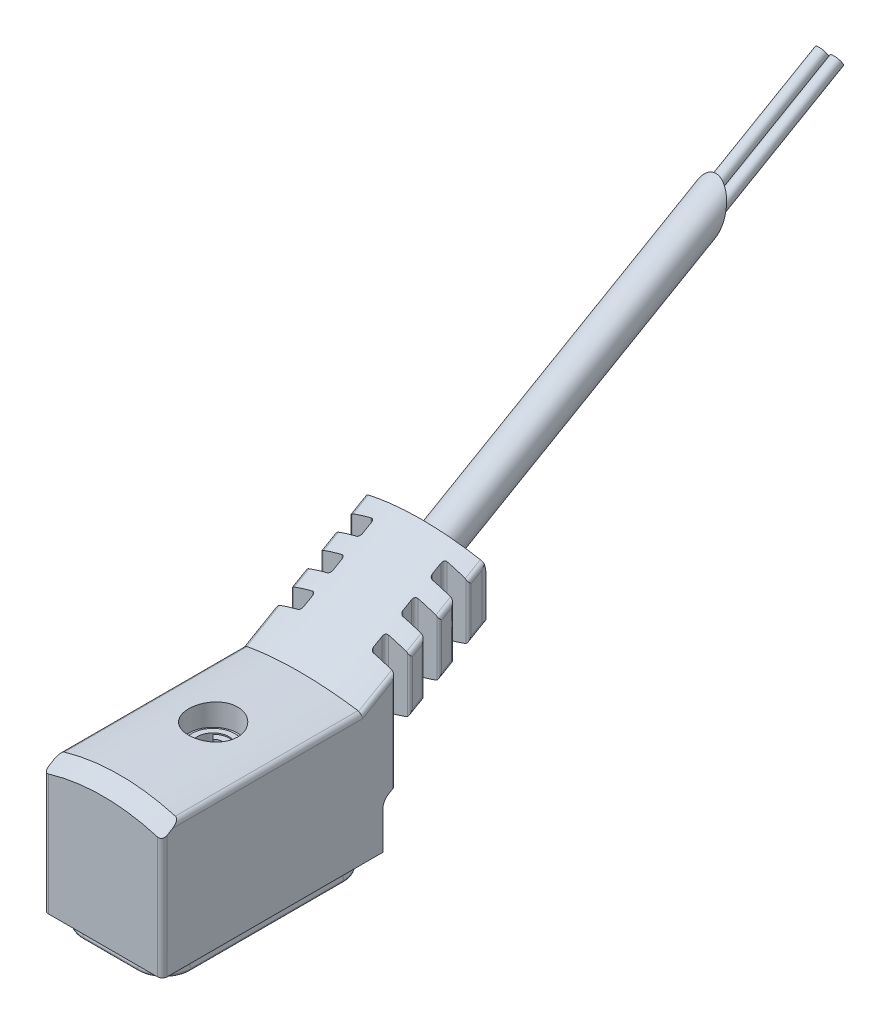
SolidWorks part; units mm, degrees
ref_plane "Front Plane" through (0, 0, 0) normal (0, 0, 1) x (1, 0, 0)
ref_plane "Top Plane" through (0, 0, 0) normal (0, 1, 0) x (1, 0, 0)
ref_plane "Right Plane" through (0, 0, 0) normal (1, 0, 0) x (0, 0, -1)
ref_plane "Plane1" through (0, 0, 0.2) normal (0, 0, 1) x (1, 0, 0)
ref_plane "Plane2" through (0, -0.0866, 0.15) normal (0, -0.5, 0.866) x (1, 0, 0)
sketch "Sketch1" plane through (0, 0, 0) normal (1, 0, 0) x (0, 0, -1)
  line L0 (-9.4, 11.35) -> (-9.4, 0)
  line L1 (-9.4, 0) -> (8.6, 0)
  line L2 (8.6, 0) -> (8.6, 3.0453)
  line L3 (9.1, 3.9113) -> (9.6, 4.2)
  line L4 (9.6, 4.2) -> (9.6, 11.35)
  line L5 (9.6, 11.35) -> (-9.4, 11.35)
  arc A0 (8.6, 3.0453) -> (9.1, 3.9113) centre (9.6, 3.0453) cw
extrude "Boss-Extrude1" add sketch "Sketch1" against normal blind 4.85 and the other way blind 4.85
sketch "Sketch2" plane through (0, 0, 0.2) normal (0, 0, 1) x (1, 0, 0)
  line L0 (-6, 15) -> (-6, 0)
  line L1 (-6, 0) -> (-4.85, 0)
  line L2 (-4.85, 0) -> (-4.85, 10.2729)
  line L3 (4.85, 10.2729) -> (4.85, 0)
  line L4 (4.85, 0) -> (6, 0)
  line L5 (6, 0) -> (6, 15)
  line L6 (6, 15) -> (-6, 15)
  arc A0 (-4.85, 10.2729) -> (-4.5257, 10.705) centre (-4.4, 10.2729) cw
  arc A1 (-4.5257, 10.705) -> (4.5257, 10.705) centre (0, -4.85) cw
  arc A2 (4.5257, 10.705) -> (4.85, 10.2729) centre (4.4, 10.2729) cw
extrude "Cut-Extrude1" cut sketch "Sketch2" along normal blind 10 and the other way blind 10
sketch "Sketch3" plane through (0, 0, 0) normal (0, 1, 0) x (1, 0, 0)
  line L0 (-8, 12.8) -> (-8, -12.2)
  line L1 (-8, -12.2) -> (8, -12.2)
  line L2 (8, -12.2) -> (8, 12.8)
  line L3 (8, 12.8) -> (-8, 12.8)
  line L4 (-4.45, -9.4) -> (4.45, -9.4)
  line L5 (4.85, -9) -> (4.85, 9.4)
  line L6 (4.65, 9.6) -> (-4.65, 9.6)
  line L7 (-4.85, 9.4) -> (-4.85, -9)
  arc A0 (-4.85, -9) -> (-4.45, -9.4) centre (-4.45, -9) ccw
  arc A1 (4.45, -9.4) -> (4.85, -9) centre (4.45, -9) ccw
  arc A2 (4.85, 9.4) -> (4.65, 9.6) centre (4.65, 9.4) ccw
  arc A3 (-4.65, 9.6) -> (-4.85, 9.4) centre (-4.65, 9.4) ccw
extrude "Cut-Extrude2" cut sketch "Sketch3" along normal blind 10
sketch "Sketch4" plane through (0, -0.0866, 0.15) normal (0, -0.5, 0.866) x (1, 0, 0)
  line L0 (4.85, 2.2157) -> (4.85, 5.4263)
  line L1 (-4.85, 5.4263) -> (-4.85, 2.2157)
  arc A0 (-4.85, 2.2157) -> (-4.5719, 1.8347) centre (-4.45, 2.2157) ccw
  arc A1 (-4.5719, 1.8347) -> (4.5719, 1.8347) centre (0, 16.121) ccw
  arc A2 (4.5719, 1.8347) -> (4.85, 2.2157) centre (4.45, 2.2157) ccw
  arc A3 (4.85, 5.4263) -> (4.5719, 5.8073) centre (4.45, 5.4263) ccw
  arc A4 (4.5719, 5.8073) -> (-4.5719, 5.8073) centre (0, -8.479) ccw
  arc A5 (-4.5719, 5.8073) -> (-4.85, 5.4263) centre (-4.45, 5.4263) ccw
extrude "Boss-Extrude2" add sketch "Sketch4" against normal blind 25
sketch "Sketch5" plane through (0, 0, 0) normal (1, 0, 0) x (0, 0, -1)
  line L0 (-9.4, 12.35) -> (-9.4, 10.55)
  line L1 (-9.4, 10.55) -> (-6.2823, 12.35)
  line L2 (-6.2823, 12.35) -> (-9.4, 12.35)
  line L3 (1.8, -4.85) -> (-2.2, -4.85) construction
revolve "Cut-Revolve1" cut sketch "Sketch5" angle 19 about L3 other way angle 19 reverse direction yes
sketch "Sketch6" plane through (0, 0, 0) normal (1, 0, 0) x (0, 0, -1)
  line L0 (15.8637, 19.2407) -> (17.5, 14.516)
  line L1 (17.5, 14.516) -> (17.5, 5)
  line L2 (17.5, 5) -> (32.5, 5)
  line L3 (32.5, 5) -> (32.5, 20)
  line L4 (32.5, 20) -> (17.5, 20)
  line L5 (17.5, 20) -> (15.8637, 19.2407)
extrude "Cut-Extrude3" cut sketch "Sketch6" along normal blind 5 and the other way blind 5
sketch "Sketch7" plane through (0, 0, 0) normal (0, 1, 0) x (1, 0, 0)
  line L0 (-6, 7.8) -> (-4.85, 7.8)
  line L1 (-4.85, 7.8) -> (-4.85, 9.4)
  line L2 (-4.65, 9.6) -> (-3.1, 9.6)
  line L3 (-2.85, 9.85) -> (-2.85, 10.55)
  line L4 (-3.1, 10.8) -> (-4.65, 10.8)
  line L5 (-4.85, 11) -> (-4.85, 11.8)
  line L6 (-4.65, 12) -> (-3.1, 12)
  line L7 (-2.85, 12.25) -> (-2.85, 12.95)
  line L8 (-3.1, 13.2) -> (-4.65, 13.2)
  line L9 (-4.85, 13.4) -> (-4.85, 14.2)
  line L10 (-4.65, 14.4) -> (-3.1, 14.4)
  line L11 (-2.85, 14.65) -> (-2.85, 15.35)
  line L12 (-3.1, 15.6) -> (-4.65, 15.6)
  line L13 (-4.85, 15.8) -> (-4.85, 16.7)
  line L14 (-4.05, 17.5) -> (4.05, 17.5)
  line L15 (4.85, 16.7) -> (4.85, 15.8)
  line L16 (4.65, 15.6) -> (3.1, 15.6)
  line L17 (2.85, 15.35) -> (2.85, 14.65)
  line L18 (3.1, 14.4) -> (4.65, 14.4)
  line L19 (4.85, 14.2) -> (4.85, 13.4)
  line L20 (4.65, 13.2) -> (3.1, 13.2)
  line L21 (2.85, 12.95) -> (2.85, 12.25)
  line L22 (3.1, 12) -> (4.65, 12)
  line L23 (4.85, 11.8) -> (4.85, 11)
  line L24 (4.65, 10.8) -> (3.1, 10.8)
  line L25 (2.85, 10.55) -> (2.85, 9.85)
  line L26 (3.1, 9.6) -> (4.65, 9.6)
  line L27 (4.85, 9.4) -> (4.85, 7.8)
  line L28 (4.85, 7.8) -> (6, 7.8)
  line L29 (6, 7.8) -> (6, 19.8)
  line L30 (6, 19.8) -> (-6, 19.8)
  line L31 (-6, 19.8) -> (-6, 7.8)
  arc A0 (-4.85, 9.4) -> (-4.65, 9.6) centre (-4.65, 9.4) cw
  arc A1 (-3.1, 9.6) -> (-2.85, 9.85) centre (-3.1, 9.85) ccw
  arc A2 (-2.85, 10.55) -> (-3.1, 10.8) centre (-3.1, 10.55) ccw
  arc A3 (-4.65, 10.8) -> (-4.85, 11) centre (-4.65, 11) cw
  arc A4 (-4.85, 11.8) -> (-4.65, 12) centre (-4.65, 11.8) cw
  arc A5 (-3.1, 12) -> (-2.85, 12.25) centre (-3.1, 12.25) ccw
  arc A6 (-2.85, 12.95) -> (-3.1, 13.2) centre (-3.1, 12.95) ccw
  arc A7 (-4.65, 13.2) -> (-4.85, 13.4) centre (-4.65, 13.4) cw
  arc A8 (-4.85, 14.2) -> (-4.65, 14.4) centre (-4.65, 14.2) cw
  arc A9 (-3.1, 14.4) -> (-2.85, 14.65) centre (-3.1, 14.65) ccw
  arc A10 (-2.85, 15.35) -> (-3.1, 15.6) centre (-3.1, 15.35) ccw
  arc A11 (-4.65, 15.6) -> (-4.85, 15.8) centre (-4.65, 15.8) cw
  arc A12 (-4.85, 16.7) -> (-4.05, 17.5) centre (-4.05, 16.7) cw
  arc A13 (4.05, 17.5) -> (4.85, 16.7) centre (4.05, 16.7) cw
  arc A14 (4.85, 15.8) -> (4.65, 15.6) centre (4.65, 15.8) cw
  arc A15 (3.1, 15.6) -> (2.85, 15.35) centre (3.1, 15.35) ccw
  arc A16 (2.85, 14.65) -> (3.1, 14.4) centre (3.1, 14.65) ccw
  arc A17 (4.65, 14.4) -> (4.85, 14.2) centre (4.65, 14.2) cw
  arc A18 (4.85, 13.4) -> (4.65, 13.2) centre (4.65, 13.4) cw
  arc A19 (3.1, 13.2) -> (2.85, 12.95) centre (3.1, 12.95) ccw
  arc A20 (2.85, 12.25) -> (3.1, 12) centre (3.1, 12.25) ccw
  arc A21 (4.65, 12) -> (4.85, 11.8) centre (4.65, 11.8) cw
  arc A22 (4.85, 11) -> (4.65, 10.8) centre (4.65, 11) cw
  arc A23 (3.1, 10.8) -> (2.85, 10.55) centre (3.1, 10.55) ccw
  arc A24 (2.85, 9.85) -> (3.1, 9.6) centre (3.1, 9.85) ccw
  arc A25 (4.65, 9.6) -> (4.85, 9.4) centre (4.65, 9.4) cw
extrude "Cut-Extrude4" cut sketch "Sketch7" along normal blind 18
sketch "Sketch8" plane through (0, 0, 0) normal (1, 0, 0) x (0, 0, -1)
  line L0 (-8.8263, -1) -> (8.0263, -1)
  line L1 (8.0263, -1) -> (7.85, 0)
  line L2 (7.85, 0) -> (-8.65, 0)
  line L3 (-8.65, 0) -> (-8.8263, -1)
extrude "Boss-Extrude3" add sketch "Sketch8" against normal blind 4.45 and the other way blind 4.45
sketch "Sketch9" plane through (0, 0, 0.2) normal (0, 0, 1) x (1, 0, 0)
  line L0 (-6, -3) -> (6, -3)
  line L1 (6, -3) -> (6, 0)
  line L2 (6, 0) -> (4.25, 0)
  line L3 (4.25, 0) -> (4.4263, -1)
  line L4 (4.4263, -1) -> (-4.4263, -1)
  line L5 (-4.4263, -1) -> (-4.25, 0)
  line L6 (-4.25, 0) -> (-6, 0)
  line L7 (-6, 0) -> (-6, -3)
extrude "Cut-Extrude5" cut sketch "Sketch9" along normal blind 9 and the other way blind 9
sketch "Sketch10" plane through (0, -0.0866, 0.15) normal (0, -0.5, 0.866) x (1, 0, 0)
  circle A0 centre (0, 3.821) radius 1.45
extrude "Boss-Extrude4" add sketch "Sketch10" against normal blind 50.5
sketch "Sketch11" plane through (0, 0, 0) normal (1, 0, 0) x (0, 0, -1)
  line L0 (37.3798, 20.6031) -> (42.0783, 18.893)
  line L1 (42.0783, 18.893) -> (45.4985, 28.2899)
  line L2 (45.4985, 28.2899) -> (40.8, 30)
  line L3 (40.8, 30) -> (37.3798, 20.6031)
extrude "Cut-Extrude6" cut sketch "Sketch11" along normal blind 3 and the other way blind 3
ref_plane "Plane3" through (0, 0, 6.65) normal (0, 0, 1) x (1, 0, 0)
sketch "Sketch12" plane through (0, 0, 6.65) normal (0, 0, 1) x (1, 0, 0)
  line L0 (-2.25, -3) -> (-6, -3)
  line L1 (-6, -3) -> (-6, 0)
  line L2 (-6, 0) -> (-4.25, 0)
  line L3 (-4.25, 0) -> (-4.3953, -0.824)
  line L4 (-4.2476, -1) -> (-2.25, -1)
  line L5 (-2.25, -1) -> (-2.25, -3)
  line L6 (-2.25, -1) -> (-2.25, -3) construction
  arc A0 (-4.3953, -0.824) -> (-4.2476, -1) centre (-4.2476, -0.85) ccw
revolve "Cut-Revolve2" cut sketch "Sketch12" angle 90 about L6 reverse direction yes
ref_plane "Plane4" through (0, 0, -5.85) normal (0, 0, 1) x (1, 0, 0)
sketch "Sketch13" plane through (0, 0, -5.85) normal (0, 0, 1) x (1, 0, 0)
  line L0 (-6, -3) -> (6, -3)
  line L1 (6, -3) -> (6, 0)
  line L2 (6, 0) -> (4.25, 0)
  line L3 (4.25, 0) -> (4.3953, -0.824)
  line L4 (4.2476, -1) -> (-4.2476, -1)
  line L5 (-4.3953, -0.824) -> (-4.25, 0)
  line L6 (-4.25, 0) -> (-6, 0)
  line L7 (-6, 0) -> (-6, -3)
  arc A0 (4.3953, -0.824) -> (4.2476, -1) centre (4.2476, -0.85) cw
  arc A1 (-4.2476, -1) -> (-4.3953, -0.824) centre (-4.2476, -0.85) cw
extrude "Cut-Extrude7" cut sketch "Sketch13" along normal blind 12.5
sketch "Sketch14" plane through (0, 0, 0) normal (1, 0, 0) x (0, 0, -1)
  line L0 (-10.2, -2) -> (9.8, -2)
  line L1 (9.8, -2) -> (9.8, 0)
  line L2 (9.8, 0) -> (7.85, 0)
  line L3 (7.85, 0) -> (7.9953, -0.824)
  line L4 (7.8476, -1) -> (-8.6476, -1)
  line L5 (-8.7953, -0.824) -> (-8.65, 0)
  line L6 (-8.65, 0) -> (-10.2, 0)
  line L7 (-10.2, 0) -> (-10.2, -2)
  arc A0 (7.9953, -0.824) -> (7.8476, -1) centre (7.8476, -0.85) cw
  arc A1 (-8.6476, -1) -> (-8.7953, -0.824) centre (-8.6476, -0.85) cw
extrude "Cut-Extrude8" cut sketch "Sketch14" along normal blind 6.45 and the other way blind 6.45
sketch "Sketch15" plane through (0, 0, 6.65) normal (0, 0, 1) x (1, 0, 0)
  line L0 (2.25, -1) -> (4.2476, -1)
  line L1 (4.3953, -0.824) -> (4.25, 0)
  line L2 (4.25, 0) -> (6, 0)
  line L3 (6, 0) -> (6, -3)
  line L4 (6, -3) -> (2.25, -3)
  line L5 (2.25, -3) -> (2.25, -1)
  line L6 (2.25, -3) -> (2.25, -1) construction
  arc A0 (4.2476, -1) -> (4.3953, -0.824) centre (4.2476, -0.85) ccw
revolve "Cut-Revolve3" cut sketch "Sketch15" angle 90 about L6 reverse direction yes
ref_plane "Plane5" through (0, 0, -5.85) normal (0, 0, 1) x (1, 0, 0)
sketch "Sketch16" plane through (0, 0, -5.85) normal (0, 0, 1) x (1, 0, 0)
  line L0 (2.25, -1) -> (4.2476, -1)
  line L1 (4.3953, -0.824) -> (4.25, 0)
  line L2 (4.25, 0) -> (6, 0)
  line L3 (6, 0) -> (6, -3)
  line L4 (6, -3) -> (2.25, -3)
  line L5 (2.25, -3) -> (2.25, -1)
  line L6 (2.25, -3) -> (2.25, -1) construction
  arc A0 (4.2476, -1) -> (4.3953, -0.824) centre (4.2476, -0.85) ccw
revolve "Cut-Revolve4" cut sketch "Sketch16" angle 90 about L6
sketch "Sketch17" plane through (0, 0, -5.85) normal (0, 0, 1) x (1, 0, 0)
  line L0 (-2.25, -3) -> (-6, -3)
  line L1 (-6, -3) -> (-6, 0)
  line L2 (-6, 0) -> (-4.25, 0)
  line L3 (-4.25, 0) -> (-4.3953, -0.824)
  line L4 (-4.2476, -1) -> (-2.25, -1)
  line L5 (-2.25, -1) -> (-2.25, -3)
  line L6 (-2.25, -1) -> (-2.25, -3) construction
  arc A0 (-4.3953, -0.824) -> (-4.2476, -1) centre (-4.2476, -0.85) ccw
revolve "Cut-Revolve5" cut sketch "Sketch17" angle 90 about L6
sketch "Sketch18" plane through (0, 0, 0) normal (1, 0, 0) x (0, 0, -1)
  line L0 (-8.6168, -1) -> (7.8168, -1)
  line L1 (7.7276, -0.9451) -> (7.25, 0)
  line L2 (7.25, 0) -> (-8.05, 0)
  line L3 (-8.05, 0) -> (-8.5276, -0.9451)
  arc A0 (7.8168, -1) -> (7.7276, -0.9451) centre (7.8168, -0.9) cw
  arc A1 (-8.5276, -0.9451) -> (-8.6168, -1) centre (-8.6168, -0.9) cw
extrude "Cut-Extrude9" cut sketch "Sketch18" along normal blind 2.25 and the other way blind 2.25
ref_plane "Plane6" through (0, 0, -5.85) normal (0, 0, 1) x (1, 0, 0)
sketch "Sketch19" plane through (0, 0, -5.85) normal (0, 0, 1) x (1, 0, 0)
  line L0 (-4.2168, -1) -> (4.2168, -1)
  line L1 (4.1276, -0.9451) -> (3.65, 0)
  line L2 (3.65, 0) -> (-3.65, 0)
  line L3 (-3.65, 0) -> (-4.1276, -0.9451)
  arc A0 (4.2168, -1) -> (4.1276, -0.9451) centre (4.2168, -0.9) cw
  arc A1 (-4.1276, -0.9451) -> (-4.2168, -1) centre (-4.2168, -0.9) cw
extrude "Cut-Extrude10" cut sketch "Sketch19" along normal blind 12.5
sketch "Sketch20" plane through (0, 0, 6.65) normal (0, 0, 1) x (1, 0, 0)
  line L0 (-2.25, -1) -> (-4.2168, -1)
  line L1 (-4.1276, -0.9451) -> (-3.65, 0)
  line L2 (-3.65, 0) -> (-2.25, 0)
  line L3 (-2.25, 0) -> (-2.25, -1)
  line L4 (-2.25, 0) -> (-2.25, -1) construction
  arc A0 (-4.2168, -1) -> (-4.1276, -0.9451) centre (-4.2168, -0.9) ccw
revolve "Cut-Revolve6" cut sketch "Sketch20" angle 360 about L4
sketch "Sketch21" plane through (0, 0, 6.65) normal (0, 0, 1) x (1, 0, 0)
  line L0 (2.25, 0) -> (3.65, 0)
  line L1 (3.65, 0) -> (4.1276, -0.9451)
  line L2 (4.2168, -1) -> (2.25, -1)
  line L3 (2.25, -1) -> (2.25, 0)
  line L4 (2.25, -1) -> (2.25, 0) construction
  arc A0 (4.1276, -0.9451) -> (4.2168, -1) centre (4.2168, -0.9) ccw
revolve "Cut-Revolve7" cut sketch "Sketch21" angle 360 about L4
sketch "Sketch22" plane through (0, 0, -5.85) normal (0, 0, 1) x (1, 0, 0)
  line L0 (-2.25, -1) -> (-4.2168, -1)
  line L1 (-4.1276, -0.9451) -> (-3.65, 0)
  line L2 (-3.65, 0) -> (-2.25, 0)
  line L3 (-2.25, 0) -> (-2.25, -1)
  line L4 (-2.25, 0) -> (-2.25, -1) construction
  arc A0 (-4.2168, -1) -> (-4.1276, -0.9451) centre (-4.2168, -0.9) ccw
revolve "Cut-Revolve8" cut sketch "Sketch22" angle 360 about L4
sketch "Sketch23" plane through (0, 0, -5.85) normal (0, 0, 1) x (1, 0, 0)
  line L0 (2.25, 0) -> (3.65, 0)
  line L1 (3.65, 0) -> (4.1276, -0.9451)
  line L2 (4.2168, -1) -> (2.25, -1)
  line L3 (2.25, -1) -> (2.25, 0)
  line L4 (2.25, -1) -> (2.25, 0) construction
  arc A0 (4.1276, -0.9451) -> (4.2168, -1) centre (4.2168, -0.9) ccw
revolve "Cut-Revolve9" cut sketch "Sketch23" angle 360 about L4
sketch "Sketch24" plane through (0, 0, 0) normal (1, 0, 0) x (0, 0, -1)
  line L0 (-0.4, 0) -> (-2.5, 0)
  line L1 (-2.5, 0) -> (-2.4651, 2)
  line L2 (-2.4651, 2) -> (-1.5425, 2)
  line L3 (-1.5425, 2) -> (-1.45, 7.3)
  line L4 (-1.45, 7.3) -> (-1.45, 8.5)
  line L5 (-1.45, 8.5) -> (-1.7, 8.5)
  line L6 (-1.7, 8.5) -> (-1.7, 9.6)
  line L7 (-1.7, 9.6) -> (-2.15, 9.6)
  line L8 (-2.15, 9.6) -> (-2.2, 9.55)
  line L9 (-2.2, 9.55) -> (-2.2, 9.5)
  line L10 (-2.2, 9.5) -> (-2.4, 9.5)
  line L11 (-2.4, 9.5) -> (-2.4, 11.35)
  line L12 (-2.4, 11.35) -> (-0.4, 11.35)
  line L13 (-0.4, 11.35) -> (-0.4, 0)
  line L14 (-0.4, 11.35) -> (-0.4, 0) construction
revolve "Cut-Revolve10" cut sketch "Sketch24" angle 360 about L14 reverse direction yes
ref_plane "Plane7" through (0, 8.5, 0) normal (0, 1, 0) x (1, 0, 0)
sketch "Sketch25" plane through (0, 8.5, 0) normal (0, 1, 0) x (1, 0, 0)
  line L0 (-1.0607, 0.6607) -> (-0.5657, 0.1657)
  line L1 (0.5657, 0.1657) -> (1.0607, 0.6607)
  arc A0 (-0.5657, 0.1657) -> (0.5657, 0.1657) centre (0, -0.4) cw
  arc A1 (1.0607, 0.6607) -> (-1.0607, 0.6607) centre (0, -0.4) ccw
extrude "Boss-Extrude5" add sketch "Sketch25" along normal blind 1
ref_plane "Plane8" through (0, 0, 0.4) normal (0, 0, 1) x (1, 0, 0)
sketch "Sketch26" plane through (0, 8.5, 0) normal (0, 1, 0) x (1, 0, 0)
  line L0 (1.0607, -1.4607) -> (0.5657, -0.9657)
  line L1 (-0.5657, -0.9657) -> (-1.0607, -1.4607)
  arc A0 (-1.0607, -1.4607) -> (1.0607, -1.4607) centre (0, -0.4) ccw
  arc A1 (0.5657, -0.9657) -> (-0.5657, -0.9657) centre (0, -0.4) cw
extrude "Boss-Extrude6" add sketch "Sketch26" along normal blind 1
ref_plane "Plane9" through (0, 2, 0) normal (0, 1, 0) x (1, 0, 0)
ref_plane "Plane10" through (0, 9.6, 0) normal (0, 1, 0) x (1, 0, 0)
ref_plane "Plane11" through (0, 0, 4.65) normal (0, 0, 1) x (1, 0, 0)
sketch "Sketch27" plane through (0, 0, 4.65) normal (0, 0, 1) x (1, 0, 0)
  line L0 (-0.5, 0) -> (0.5, 0)
  line L1 (0.5, 0) -> (0.3092, 0.5243)
  line L2 (0.3092, 0.5243) -> (0.4065, 6.1)
  line L3 (0.4065, 6.1) -> (-0.4065, 6.1)
  line L4 (-0.4065, 6.1) -> (-0.3092, 0.5243)
  line L5 (-0.3092, 0.5243) -> (-0.5, 0)
extrude "Cut-Extrude11" cut sketch "Sketch27" along normal blind 1.55 and the other way blind 1.55
ref_plane "Plane12" through (0, 0, -3.85) normal (0, 0, 1) x (1, 0, 0)
sketch "Sketch28" plane through (0, 0, -3.85) normal (0, 0, 1) x (1, 0, 0)
  line L0 (-0.5, 0) -> (0.5, 0)
  line L1 (0.5, 0) -> (0.3092, 0.5243)
  line L2 (0.3092, 0.5243) -> (0.4065, 6.1)
  line L3 (0.4065, 6.1) -> (-0.4065, 6.1)
  line L4 (-0.4065, 6.1) -> (-0.3092, 0.5243)
  line L5 (-0.3092, 0.5243) -> (-0.5, 0)
extrude "Cut-Extrude12" cut sketch "Sketch28" along normal blind 1.55 and the other way blind 1.55
ref_plane "Plane13" through (0, 24.9134, -43.1513) normal (0, -0.5, 0.866) x (1, 0, 0)
ref_plane "Plane14" through (0, 4.9134, -8.5103) normal (0, -0.5, 0.866) x (1, 0, 0)
sketch "Sketch29" plane through (0, 4.9134, -8.5103) normal (0, -0.5, 0.866) x (1, 0, 0)
  circle A0 centre (0.6, 3.821) radius 0.5
extrude "Boss-Extrude7" add sketch "Sketch29" against normal blind 50
sketch "Sketch30" plane through (0, 4.9134, -8.5103) normal (0, -0.5, 0.866) x (1, 0, 0)
  circle A0 centre (-0.6, 3.821) radius 0.5
extrude "Boss-Extrude8" add sketch "Sketch30" against normal blind 50
ref_plane "ANBAU XY" through (0, 0, 0.4) normal (0, 0, 1) x (1, 0, 0)
ref_plane "ANBAU XZ" through (0, 0, 0) normal (1, 0, 0) x (0, 0, -1)
ref_plane "ANBAU YZ" through (0, 0, 0) normal (0, 1, 0) x (1, 0, 0)
ref_axis "ANBAU X" through (0, -50, 0.4) along (0, 1, 0)
ref_axis "ANBAU Y" through (80.9, 0, 0.4) along (-1, 0, 0)
ref_axis "ANBAU Z" through (0, 0, 50) along (0, 0, -1)
sketch3d "ANBAU"
  point P0 (0, 0, 0.4)
ref_plane "FURCHS XY" through (0, 9.6, 0) normal (0, -1, 0) x (-1, 0, 0)
ref_plane "FURCHS XZ" through (0, 0, 0.4) normal (0, 0, -1) x (-1, 0, 0)
ref_plane "FURCHS YZ" through (0, 0, 0) normal (1, 0, 0) x (0, 0, -1)
ref_axis "FURCHS X" through (-80.9, 9.6, 0.4) along (1, 0, 0)
ref_axis "FURCHS Y" through (0, 9.6, -50) along (0, 0, 1)
ref_axis "FURCHS Z" through (0, -50, 0.4) along (0, 1, 0)
sketch3d "FURCHS"
  point P0 (0, 9.6, 0.4)
ref_plane "ISO7045 XY" through (0, 2, 0) normal (0, -1, 0) x (-1, 0, 0)
ref_plane "ISO7045 XZ" through (0, 0, 0.4) normal (0, 0, -1) x (-1, 0, 0)
ref_plane "ISO7045 YZ" through (0, 0, 0) normal (1, 0, 0) x (0, 0, -1)
ref_axis "ISO7045 X" through (-80.9, 2, 0.4) along (1, 0, 0)
ref_axis "ISO7045 Y" through (0, 2, -50) along (0, 0, 1)
ref_axis "ISO7045 Z" through (0, -50, 0.4) along (0, 1, 0)
sketch3d "ISO7045"
  point P0 (0, 2, 0.4)
ref_plane "STECKER XY" through (0, 24.9134, -43.1513) normal (0, -0.5, 0.866) x (1, 0, 0)
ref_plane "STECKER XZ" through (0, 3.3091, 1.9105) normal (0, -0.866, -0.5) x (-1, 0, 0)
ref_plane "STECKER YZ" through (0, 0, 0) normal (1, 0, 0) x (0, 0, -1)
ref_axis "STECKER X" through (-80.9, 28.2225, -41.2408) along (1, 0, 0)
ref_axis "STECKER Y" through (0, -18.3879, -68.1513) along (0, 0.866, 0.5)
ref_axis "STECKER Z" through (0, -42.2955, 80.9) along (0, 0.5, -0.866)
sketch3d "STECKER"
  point P0 (0, 28.2225, -41.2408)
